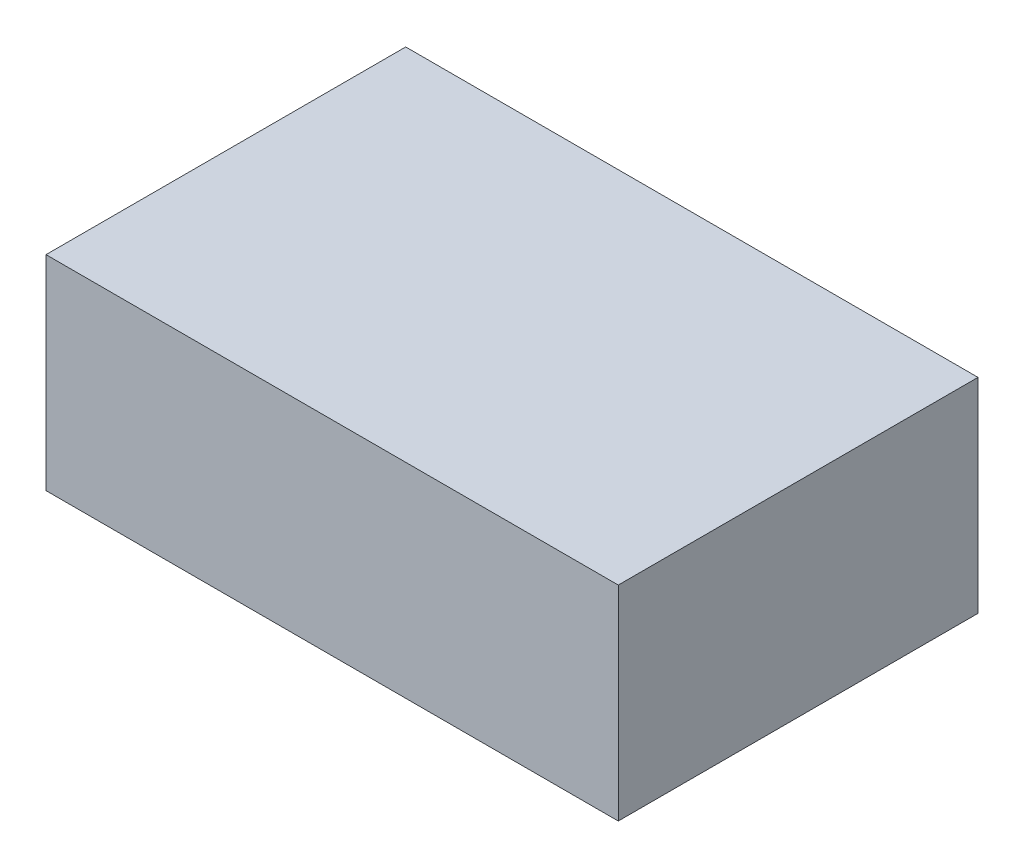
SolidWorks part; units mm, degrees
ref_plane "Front Plane" through (0, 0, 0) normal (0, 0, 1) x (1, 0, 0)
ref_plane "Top Plane" through (0, 0, 0) normal (0, 1, 0) x (1, 0, 0)
ref_plane "Right Plane" through (0, 0, 0) normal (1, 0, 0) x (0, 0, -1)
sketch "Sketch1" plane through (0, 0, 0) normal (0, 1, 0) x (1, 0, 0)
  line L1 (15.2482, 39.7339) -> (43.2482, 39.7339)
  line L2 (15.2482, 39.7339) -> (15.2482, 22.1339)
  line L3 (15.2482, 22.1339) -> (43.2482, 22.1339)
  line L4 (43.2482, 39.7339) -> (43.2482, 22.1339)
  line L5 (15.2482, 39.7339) -> (43.2482, 22.1339) construction
  line L6 (15.2482, 22.1339) -> (43.2482, 39.7339) construction
  point P0 (29.2482, 30.9339)
  dimension "D1" = 17.6
  dimension "D2" = 28
extrude "Boss-Extrude1" add sketch "Sketch1" along normal blind 10
